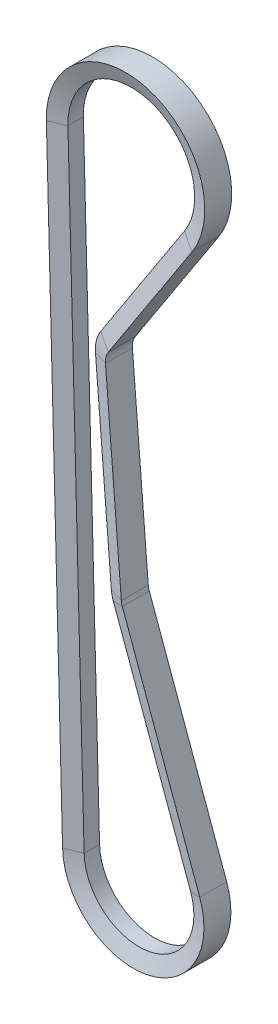
SolidWorks part; units mm, degrees
ref_plane "Front Plane" through (0, 0, 0) normal (0, 0, 1) x (1, 0, 0)
ref_plane "Top Plane" through (0, 0, 0) normal (0, 1, 0) x (1, 0, 0)
ref_plane "Right Plane" through (0, 0, 0) normal (1, 0, 0) x (0, 0, -1)
sketch "Sketch2" plane through (0, 0, 0) normal (0, 0, 1) x (1, 0, 0)
  line L0 (0, 0) -> (1, 0) construction
  line L1 (0, 0) -> (0, 1) construction
  line L12 (-24.9915, -0.65) -> (-30.7109, 219.2552)
  line L14 (20.7488, 204.7124) -> (-8.8187, 159.2709)
  line L15 (-9.8258, 155.2988) -> (-4.2167, 85.5239)
  line L16 (-3.8558, 83.8654) -> (23.4988, 8.5328)
  arc A4 (-30.7109, 219.2552) -> (20.7488, 204.7124) centre (-2.7204, 219.9832) cw
  arc A7 (23.4988, 8.5328) -> (-24.9915, -0.65) centre (0, 0) cw
  arc A8 (-8.8187, 159.2709) -> (-9.8258, 155.2988) centre (-3.4962, 155.8077) ccw
  arc A9 (-4.2167, 85.5239) -> (-3.8558, 83.8654) centre (2.1129, 86.0328) ccw
ref_plane "Plane4" through (23.4988, 8.5328, 0) normal (0.3413, -0.94, 0) x (-0.94, -0.3413, 0)
sketch "Sketch3" plane through (23.4988, 8.5328, 0) normal (0.3413, -0.94, 0) x (-0.94, -0.3413, 0)
  line L0 (0, -4.7625) -> (0, 4.7625)
  line L1 (0, -4.7625) -> (5.588, -2.7286)
  line L2 (5.588, -2.7286) -> (5.588, 2.7286)
  line L3 (5.588, 2.7286) -> (0, 4.7625)
  line L4 (0, 0) -> (5.588, 0) construction
  dimension "D1" = 9.525
  dimension "D2" = 5.588
  dimension "D3" = 40
sweep "Sweep1" add profiles "Sketch3" path "Sketch2"
